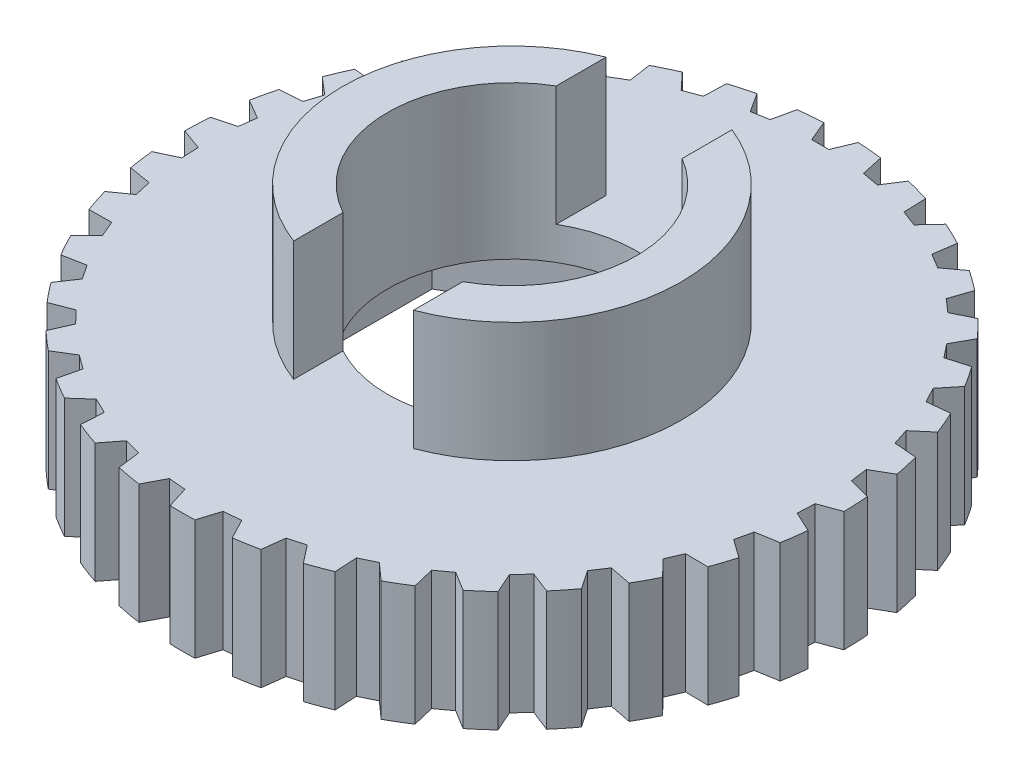
SolidWorks part; units mm, degrees
ref_plane "前视基准面" through (0, 0, 0) normal (0, 0, 1) x (1, 0, 0)
ref_plane "上视基准面" through (0, 0, 0) normal (0, 1, 0) x (1, 0, 0)
ref_plane "右视基准面" through (0, 0, 0) normal (1, 0, 0) x (0, 0, -1)
sketch "草图1" plane through (0, 0, 0) normal (0, 1, 0) x (1, 0, 0)
  circle A0 centre (0, 0) radius 5.65
  circle A1 centre (0, 0) radius 11
  circle A2 centre (0, 0) radius 4.15
  dimension "D1" = 11.3
  dimension "D2" = 22
  dimension "D3" = 1.5
extrude "凸台-拉伸1" add sketch "草图1" along normal blind 8 contours A0 A2 region at (-5.4902, 0, 0)
extrude "凸台-拉伸2" add sketch "草图1<3>" along normal blind 4 contours A1 A0 region at (-10.6889, 0, 0)
sketch "草图1<3>" plane through (0, 0, 0) normal (0, 1, 0) x (1, 0, 0) same geometry as "草图1"
sketch "草图2" plane through (0, 0, 0) normal (0, -1, 0) x (1, 0, 0)
  line L0 (-6, -3.4641) -> (-6, 3.4641) construction
  line L1 (-6, 3.4641) -> (0, 6.9282) construction
  line L2 (0, 6.9282) -> (6, 3.4641) construction
  line L3 (6, 3.4641) -> (6, -3.4641) construction
  line L4 (6, -3.4641) -> (0, -6.9282) construction
  line L5 (0, -6.9282) -> (-6, -3.4641) construction
  line L6 (0, -7.2746) -> (-6.3, -3.6373)
  line L7 (-6.3, -3.6373) -> (-6.3, 3.6373)
  line L8 (-6.3, 3.6373) -> (0, 7.2746)
  line L9 (0, 7.2746) -> (6.3, 3.6373)
  line L10 (6.3, 3.6373) -> (6.3, -3.6373)
  line L11 (6.3, -3.6373) -> (0, -7.2746)
  circle A0 centre (0, 0) radius 6.9282 construction
  dimension "D1" = 12
  dimension "D2" = 0.3
extrude "切除-拉伸1" cut sketch "草图2" against normal blind 2.9
sketch "草图4" plane through (0, 8, 0) normal (0, 1, 0) x (1, 0, 0)
  line L0 (0, 4.1459) -> (0, 5.647) construction
  line L1 (-2.1, 5.2452) -> (-2.1, 3.5795)
  line L2 (2.1, 5.2452) -> (2.1, 3.5795)
  line L3 (2, -3.6363) -> (2, -5.2842)
  line L4 (-2, -3.6363) -> (-2, -5.2842)
  circle A0 centre (0, 0) radius 4.15 construction
  circle A1 centre (0, 0) radius 5.65 construction
  circle A2 centre (0, 0) radius 5.65 construction
  arc A3 (-2, -3.6363) -> (2, -3.6363) centre (0, 0) ccw
  arc A4 (-2, -5.2842) -> (2, -5.2842) centre (0, 0) ccw
  arc A5 (-2.1, 5.2452) -> (-2, -5.2842) centre (0, 0) ccw construction
  arc A6 (-2.1, 3.5795) -> (-2, -3.6363) centre (0, 0) ccw construction
  arc A7 (2, -5.2842) -> (2.1, 5.2452) centre (0, 0) ccw construction
  arc A8 (2.1, 5.2452) -> (-2.1, 5.2452) centre (0, 0) ccw
  arc A9 (2, -3.6363) -> (2.1, 3.5795) centre (0, 0) ccw construction
  arc A10 (2.1, 3.5795) -> (-2.1, 3.5795) centre (0, 0) ccw
  dimension "D1" = 2.1
  dimension "D2" = 2
extrude "切除-拉伸3" cut sketch "草图4" against normal up to surface (4 mm away) up to face at (0, 4, 5.65)
sketch "草图5" plane through (0, 4, 0) normal (0, 1, 0) x (1, 0, 0)
  line L0 (-0.574, 10.985) -> (0, 9.5992)
  line L1 (0, 9.5992) -> (0.574, 10.985)
  line L2 (0, 9.5992) -> (0, 0) construction
  line L3 (-0.287, 10.2921) -> (0.287, 10.2921)
  circle A0 centre (0, 0) radius 11 construction
  arc A1 (0.574, 10.985) -> (-0.574, 10.985) centre (0, 0) ccw
  arc A2 (-0.574, 10.985) -> (0.574, 10.985) centre (0, 0) ccw construction
  point P10 (-0.574, 10.985)
  circle M11 centre (0, 0) radius 11
  dimension "D1" = 45
  dimension "D2" = 1.5
extrude "切除-拉伸4" cut sketch "草图5" against normal blind 10 contours L0 L3 L1 M11 region at (0, 4, -10.683)
pattern_circular "阵列(圆周)1" count 35 over 360 about axis through (0, 4, 0) along (0, 1, 0) of "切除-拉伸4"
